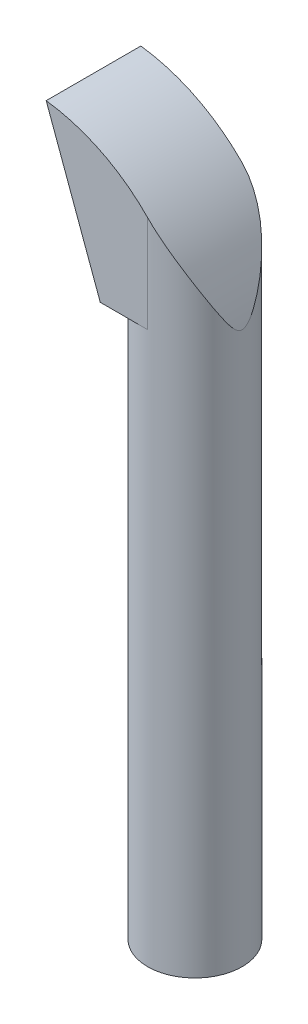
SolidWorks part; units mm, degrees
ref_plane "Front Plane" through (0, 0, 0) normal (0, 0, 1) x (1, 0, 0)
ref_plane "Top Plane" through (0, 0, 0) normal (0, 1, 0) x (1, 0, 0)
ref_plane "Right Plane" through (0, 0, 0) normal (1, 0, 0) x (0, 0, -1)
sketch "Sketch1" plane through (0, 0, 0) normal (0, 1, 0) x (1, 0, 0)
  circle A0 centre (0, 0) radius 11
  circle A1 centre (0, 0) radius 13.5
  dimension "D1" = 22
  dimension "D2" = 27
extrude "Boss-Extrude1" add sketch "Sketch1" along normal blind 152.4
sketch "Sketch2" plane through (0, 152.4, 0) normal (0, 1, 0) x (1, 0, 0)
  circle A2 centre (0, 0) radius 13.5
extrude "Boss-Extrude2" add sketch "Sketch2" along normal blind 5
sketch "Sketch4" plane through (0, 0, 0) normal (0, 0, 1) x (1, 0, 0)
  line L0 (-11.0231, 157.4) -> (13.5, 157.4)
  line L1 (13.5, 157.4) -> (-13.5, 157.4) construction
  line L5 (-13.5, 157.4) -> (-28.9264, 199.5218)
  line L6 (-11.0231, 157.4) -> (-13.5, 157.4)
  arc A0 (13.5, 157.4) -> (-28.9264, 199.5218) centre (-35.1223, 150.8535) ccw
  point P1 (-35.2461, 203.0673)
  point P5 (-28.9264, 199.5218)
extrude "Boss-Extrude3" add sketch "Sketch4" along normal blind 15 and the other way blind 15
sketch "Sketch6" plane through (0, 157.4, 0) normal (0, -1, 0) x (1, 0, 0)
  line L0 (0, -13.5) -> (-22.8315, -13.5)
  line L1 (-22.4236, -20.0913) -> (15.3878, -20.0913)
  line L3 (-22.4236, 20.0658) -> (15.3878, 20.0658)
  line L4 (15.3878, -20.0913) -> (15.3878, 20.0658)
  line L5 (-22.8315, -13.5) -> (-32.3107, -13.5)
  line L7 (-41.1135, -20.8621) -> (-22.4236, -20.0913)
  line L8 (0, 13.5) -> (-30.5693, 13.5)
  line L10 (-41.1135, -20.8621) -> (-41.1135, -13.5)
  line L11 (-41.1135, -13.5) -> (-32.3107, -13.5)
  line L12 (-30.5693, 13.5) -> (-41.5531, 13.317)
  line L13 (-41.5531, 13.317) -> (-41.1135, 20.0658)
  line L14 (-41.1135, 20.0658) -> (-22.4236, 20.0658)
  arc A1 (0, -13.5) -> (0, 13.5) centre (0, 0) ccw
  dimension "D1" = 9.4792
extrude "Cut-Extrude3" cut sketch "Sketch6" against normal blind 60
